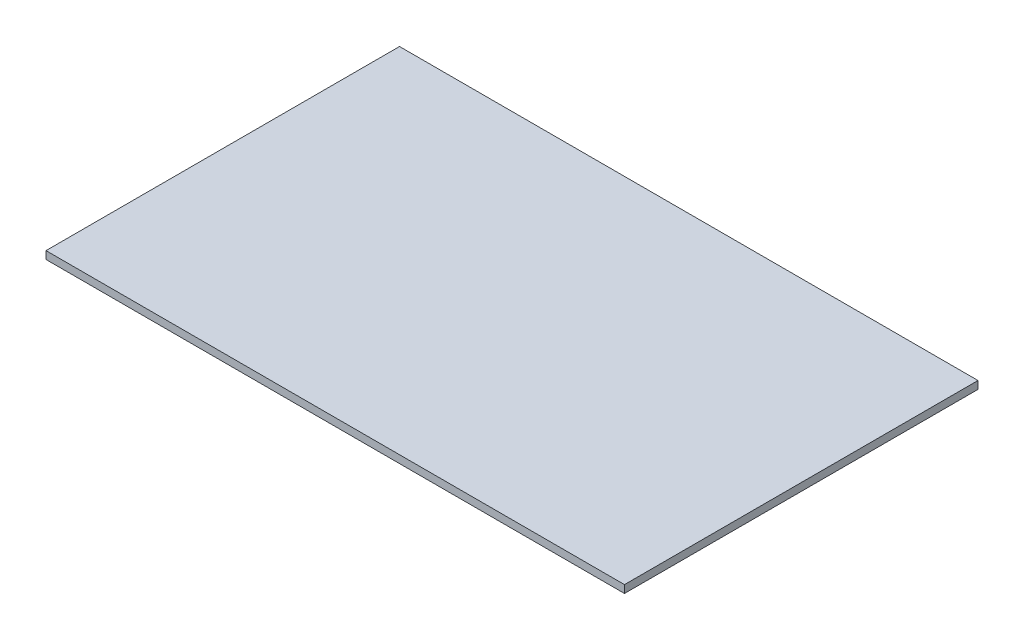
SolidWorks part; units mm, degrees
material "Oak"
ref_plane "Front Plane" through (0, 0, 0) normal (0, 0, 1) x (1, 0, 0)
ref_plane "Top Plane" through (0, 0, 0) normal (0, 1, 0) x (1, 0, 0)
ref_plane "Right Plane" through (0, 0, 0) normal (1, 0, 0) x (0, 0, -1)
sketch "Sketch2" plane through (0, 0, 0) normal (0, 1, 0) x (1, 0, 0)
  line L1 (0, 0) -> (450, 0)
  line L2 (0, 0) -> (0, 275)
  line L3 (0, 275) -> (450, 275)
  line L4 (450, 0) -> (450, 275)
  dimension "D1" = 275
  dimension "D2" = 450
extrude "Boss-Extrude1" add sketch "Sketch2" along normal blind 6
sketch "Sketch18" plane through (0, 0, 0) normal (0, -1, 0) x (1, 0, 0)
  line L0 (0, -137.5) -> (450, -137.5) construction
  line L1 (0, -275) -> (0, 0) construction
  line L2 (450, 0) -> (450, -275) construction
  line L3 (120, -227.5) -> (120, -47.5) construction
  line L5 (77.5736, -95.0736) -> (162.4264, -179.9264) construction
  circle A0 centre (120, -47.5) radius 3
  circle A1 centre (225, -47.5) radius 3
  circle A2 centre (330, -47.5) radius 3
  circle A3 centre (330, -227.5) radius 3
  circle A4 centre (225, -227.5) radius 3
  circle A5 centre (120, -227.5) radius 3
  circle A6 centre (120, -137.5) radius 60
  circle A7 centre (155.3553, -172.8553) radius 3
  circle A9 centre (85.3553, -172.8553) radius 3
  circle A10 centre (85.3553, -102.8553) radius 3
  circle A11 centre (155.3553, -102.8553) radius 3
  circle A12 centre (120, -137.5) radius 50
  circle A13 centre (70, -137.5) radius 3
  circle A14 centre (170, -137.5) radius 3
  point P22 (120, -137.5)
  point P26 (120, -137.5)
  point P38 (120.3553, -137.8553)
  dimension "D3" = 105
  dimension "D6" = 100
  dimension "D8" = 6
  dimension "D10" = 4
  dimension "D11" = 45
  dimension "D12" = 120
  dimension "D13" = 6
  dimension "D14" = 6
  dimension "D15" = 70
  dimension "D1" = 120
  dimension "D2" = 120
  dimension "D4" = 105
  dimension "D5" = 180
  dimension "D7" = 45
  dimension "D9" = 50
extrude "Cut-Extrude8" cut sketch "Sketch18" against normal mid plane 31 rebuild error yes
